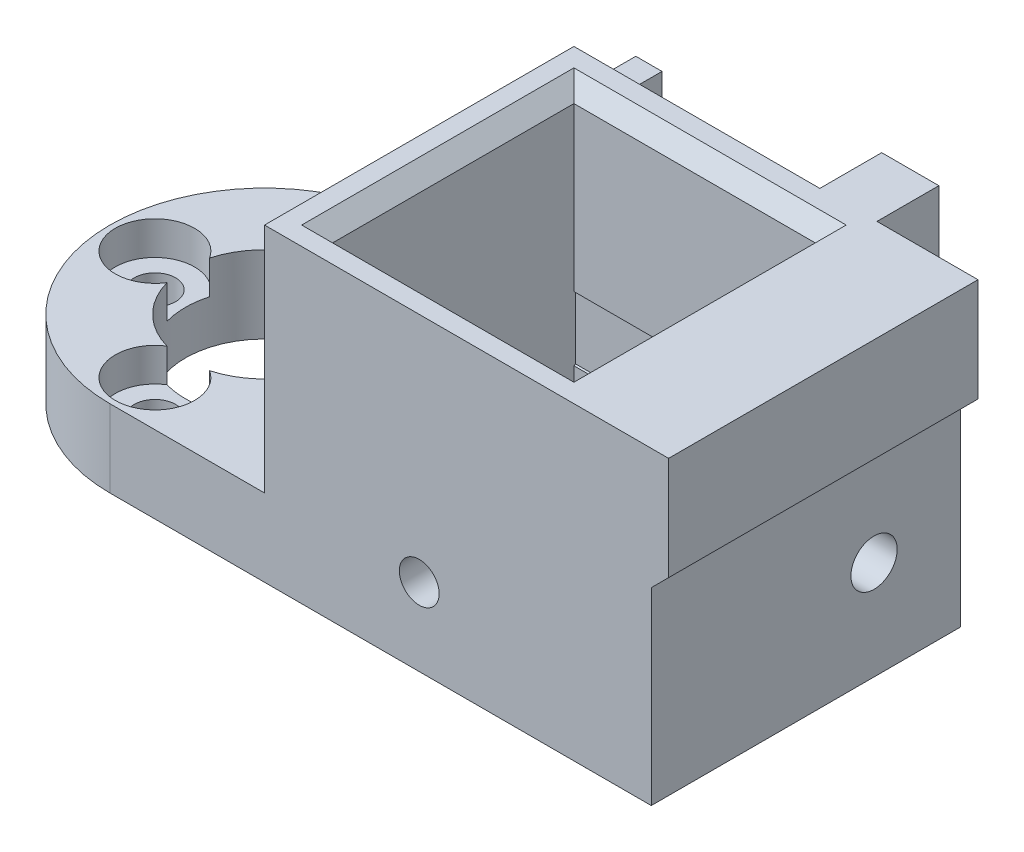
SolidWorks part; units mm, degrees
ref_plane "Front Plane" through (0, 0, 0) normal (0, 0, 1) x (1, 0, 0)
ref_plane "Top Plane" through (0, 0, 0) normal (0, 1, 0) x (1, 0, 0)
ref_plane "Right Plane" through (0, 0, 0) normal (1, 0, 0) x (0, 0, -1)
sketch "Sketch1" plane through (0, 0, 0) normal (0, 1, 0) x (1, 0, 0)
  line L1 (-12.7, 12.7) -> (12.7, 12.7)
  line L2 (-12.7, 12.7) -> (-12.7, -12.7)
  line L3 (-12.7, -12.7) -> (12.7, -12.7)
  line L4 (12.7, 12.7) -> (12.7, -12.7)
  line L5 (-12.7, 12.7) -> (12.7, -12.7) construction
  line L6 (-12.7, -12.7) -> (12.7, 12.7) construction
  line L7 (-9.906, -9.906) -> (9.906, -9.906)
  line L8 (-9.906, -9.906) -> (-9.906, 9.906)
  line L9 (-9.906, 9.906) -> (9.906, 9.906)
  line L10 (9.906, -9.906) -> (9.906, 9.906)
  line L11 (-9.906, -9.906) -> (9.906, 9.906) construction
  line L12 (-9.906, 9.906) -> (9.906, -9.906) construction
  point P0 (0, 0)
  point P6 (0, 0)
  dimension "D1" = 25.4
  dimension "D2" = 19.812
extrude "Boss-Extrude1" add sketch "Sketch1" along normal blind 25.4
sketch "Sketch4" plane through (12.7, 0, 0) normal (1, 0, 0) x (0, 0, -1)
  line L4 (-12.7, 0) -> (12.7, 0)
  line L5 (12.7, 0) -> (12.7, 25.4)
  line L6 (12.7, 25.4) -> (-12.7, 25.4)
  line L7 (-12.7, 25.4) -> (-12.7, 0)
  line L8 (-12.7, 0) -> (12.7, 0)
  line L9 (12.7, 0) -> (12.7, 25.4)
  line L10 (12.7, 25.4) -> (-12.7, 25.4)
  line L11 (-12.7, 25.4) -> (-12.7, 0)
  dimension "D1" = 0
extrude "Boss-Extrude2" add sketch "Sketch4" along normal blind 6.35
hole_wizard "#6 Clearance Hole2" positions "Sketch5" profile "Sketch6" hole size "#6" standard "ANSI Inch"
sketch "Sketch5" plane through (19.05, 0, 0) normal (1, 0, 0) x (0, 0, -1)
  point P0 (5.588, 8.128)
sketch "Sketch6" plane through (19.05, 8.128, -5.588) normal (0, 1, 0) x (0, 0, -1)
  line L0 (0, 0) -> (0, 9.144)
  line L1 (0, 9.144) -> (1.8986, 9.144)
  line L2 (1.8986, 9.144) -> (1.8986, 0)
  line L5 (1.8986, 0) -> (0, 0)
  line L11 (0, -6.35) -> (0, 107.95) construction
  dimension "Thru Hole Dia." = 3.7973
  dimension "Thru Hole Depth" = 9.144
sketch "Sketch7" plane through (9.906, 0, 0) normal (-1, 0, 0) x (0, 0, 1)
  line L1 (-5.588, 13.2606) -> (-10.033, 10.6943)
  line L2 (-10.033, 10.6943) -> (-10.033, 5.5617)
  line L3 (-10.033, 5.5617) -> (-5.588, 2.9954)
  line L4 (-5.588, 2.9954) -> (-1.143, 5.5617)
  line L5 (-1.143, 5.5617) -> (-1.143, 10.6943)
  line L6 (-1.143, 10.6943) -> (-5.588, 13.2606)
  circle A0 centre (-5.588, 8.128) radius 4.445 construction
  dimension "D1" = 8.89
extrude "Cut-Extrude1" cut sketch "Sketch7" against normal blind 5.08 and the other way up to surface other way up to face at (-9.906, 12.7, 0)
sketch "Sketch8" plane through (19.05, 0, 0) normal (1, 0, 0) x (0, 0, -1)
  line L0 (12.7, 15.24) -> (-38.1, 15.24) construction
  line L1 (12.7, 15.24) -> (-38.1, 15.24) construction
  line L2 (12.7, 15.494) -> (-12.7, 15.494)
  line L3 (12.7, 15.494) -> (-38.1, 15.494) construction
  line L7 (-12.7, 25.4) -> (-12.7, 0)
  line L8 (-12.7, 0) -> (12.7, 0)
  line L9 (12.7, 0) -> (12.7, 25.4)
  line L10 (12.7, 25.4) -> (-12.7, 25.4)
  line L11 (-12.7, 25.4) -> (-12.7, 15.494)
  line L13 (12.7, 15.494) -> (12.7, 25.4)
  line L14 (12.7, 25.4) -> (-12.7, 25.4)
  dimension "D1" = 0.254
extrude "Boss-Extrude4" add sketch "Sketch8" along normal up to surface (1.4224 mm away)
sketch "Sketch9" plane through (0, 0, 0) normal (0, -1, 0) x (1, 0, 0)
  line L0 (-12.7, -12.7) -> (-12.7, 12.7) construction
  line L1 (-12.7, -12.7) -> (-12.7, 12.7)
  line L2 (-12.7, 12.7) -> (-38.1, 12.7)
  line L3 (-38.1, 12.7) -> (-38.1, -12.7)
  line L4 (-38.1, -12.7) -> (-12.7, -12.7)
  dimension "D1" = 25.4
extrude "Boss-Extrude5" add sketch "Sketch9" against normal blind 6.35
sketch "Sketch10" plane through (0, 6.35, 0) normal (0, 1, 0) x (1, 0, 0)
  line L0 (-38.1, 12.7) -> (-12.7, 12.7) construction
  line L1 (-38.1, -12.7) -> (-38.1, 12.7) construction
  circle A0 centre (-25.4, 0) radius 6.5
  point P4 (-25.4, 12.7)
  point P7 (-38.1, 0)
  dimension "D1" = 13
extrude "Cut-Extrude2" cut sketch "Sketch10" against normal up to next
hole_wizard "M3 Clearance Hole1" positions "Sketch12" profile "Sketch13" hole size "M3" standard "ANSI Metric" end condition up to next
sketch "Sketch12" plane through (0, 6.35, 0) normal (0, 1, 0) x (1, 0, 0)
  line L0 (-38.1, 12.7) -> (-12.7, 12.7) construction
  circle A0 centre (-25.4, 0) radius 6.5 construction
  point P0 (-25.4, 9)
  point P9 (-25.4, 12.7)
  dimension "D1" = 9
sketch "Sketch13" plane through (-25.4, 6.35, -9) normal (1, 0, 0) x (0, 0, 1)
  line L0 (0, 0) -> (0, 6.35)
  line L1 (0, 6.35) -> (1.7, 6.35)
  line L2 (1.7, 6.35) -> (1.7, 0)
  line L5 (1.7, 0) -> (0, 0)
  line L11 (0, -6.35) -> (0, 107.95) construction
  dimension "Thru Hole Dia." = 3.4
  dimension "Thru Hole Depth" = 6.35
pattern_circular "CirPattern1" count 4 over 360 about axis through (-25.4, 0, 0) along (0, 1, 0) of "M3 Clearance Hole1"
fillet "Fillet1" radius 12.7 2 edges at (-38.1, 3.175, 12.7) (-38.1, 3.175, -12.7)
sketch "Sketch15" plane through (0, 0, 0) normal (0, -1, 0) x (1, 0, 0)
  line L0 (9.906, -9.906) -> (-9.906, -9.906) construction
  line L1 (9.906, 9.906) -> (9.906, -9.906) construction
  line L2 (-9.906, 9.906) -> (9.906, 9.906) construction
  line L3 (-9.906, -9.906) -> (-9.906, 9.906) construction
  line L4 (9.906, -9.906) -> (-9.906, -9.906)
  line L5 (9.906, 9.906) -> (9.906, -9.906)
  line L6 (-9.906, 9.906) -> (9.906, 9.906)
  line L7 (-9.906, -9.906) -> (-9.906, 9.906)
  line L8 (-8.001, 8.001) -> (8.001, 8.001)
  line L9 (8.001, 8.001) -> (8.001, -8.001)
  line L10 (8.001, -8.001) -> (-8.001, -8.001)
  line L11 (-8.001, -8.001) -> (-8.001, 8.001)
  dimension "D1" = 1.905
extrude "Boss-Extrude6" add sketch "Sketch15" against normal blind 2.54
sketch "Sketch17" plane through (0, 6.35, 0) normal (0, 1, 0) x (1, 0, 0)
  circle A0 centre (-25.4, 9) radius 3.25
  dimension "D1" = 6.5
extrude "Cut-Extrude4" cut sketch "Sketch17" against normal offset from surface (2.75 mm away) 2.75 up to face at (-34.4, 6.35, 1.7)
pattern_circular "CirPattern2" count 4 over 360 about axis through (-25.4, 0, 0) along (0, 1, 0) of "Cut-Extrude4"
fillet "Fillet4" radius 1.27 8 edges at (0, 2.54, 8.001) (0, 0, 8.001) (-8.001, 2.54, 0) (8.001, 2.54, 0) (-8.001, 0, 0) (8.001, 0, 0) (0, 2.54, -8.001) (0, 0, -8.001)
hole_wizard "#4 Clearance Hole1" positions "Sketch20" profile "Sketch21" hole size "#4" standard "ANSI Inch" end condition through all
sketch "Sketch20" plane through (0, 0, -12.7) normal (0, 0, -1) x (-1, 0, 0)
  line L0 (-9.906, 25.4) -> (9.906, 25.4) construction
  line L1 (-19.05, 0) -> (25.4, 0) construction
  point P0 (0, 6.35)
  point P5 (0, 25.4)
  dimension "D1" = 6.35
sketch "Sketch21" plane through (0, 6.35, -12.7) normal (1, 0, 0) x (0, 1, 0)
  line L0 (0, 0) -> (0, 25.4)
  line L1 (0, 25.4) -> (1.6319, 25.4)
  line L2 (1.6319, 25.4) -> (1.6319, 0)
  line L5 (1.6319, 0) -> (0, 0)
  line L11 (0, -6.35) -> (0, 107.95) construction
  dimension "Thru Hole Dia." = 3.2639
  dimension "Thru Hole Depth" = 25.4
chamfer "Chamfer1" distance 1.4224 angle 45 1 edges at (20.4724, 15.494, 0)
chamfer "Chamfer2" distance 1.27 angle 45 4 edges at (0, 25.4, 9.906) (9.906, 25.4, 0) (0, 25.4, -9.906) (-9.906, 25.4, 0)
sketch "Sketch22" plane through (0, 0, -12.7) normal (0, 0, -1) x (-1, 0, 0)
  line L0 (-19.05, 0) -> (25.4, 0) construction
  line L1 (7.62, 0) -> (-2.54, 0)
  line L2 (7.62, 0) -> (7.62, 2.54)
  line L3 (7.62, 2.54) -> (-2.54, 2.54)
  line L4 (-2.54, 0) -> (-2.54, 2.54)
  line L5 (12.7, 25.4) -> (12.7, 6.35) construction
  dimension "D1" = 2.54
  dimension "D2" = 10.16
  dimension "D3" = 5.08
extrude "Boss-Extrude7" add sketch "Sketch22" along normal blind 5.08
chamfer "Chamfer3" distance 2.54 angle 45 2 edges at (-7.62, 1.27, -17.78) (2.54, 1.27, -17.78)
sketch "Sketch23" plane through (0, 0, -12.7) normal (0, 0, -1) x (-1, 0, 0)
  line L0 (-20.4724, 25.4) -> (12.7, 25.4) construction
  line L1 (12.7, 25.4) -> (12.7, 6.35) construction
  line L2 (-20.4724, 25.4) -> (12.7, 25.4)
  line L3 (12.7, 25.4) -> (12.7, 6.35)
  line L4 (12.7, 22.16) -> (10.547, 22.16)
  line L5 (10.547, 22.16) -> (10.547, 12.152)
  line L6 (10.547, 12.152) -> (9.023, 12.152)
  line L7 (9.023, 12.152) -> (9.023, 9.999)
  line L8 (9.023, 9.999) -> (12.7, 9.999)
  line L9 (-10.027, 12.66) -> (-12.18, 12.66)
  line L10 (-12.18, 12.66) -> (-12.18, 25.4)
  line L11 (-12.18, 25.4) -> (-7.487, 25.4)
  line L12 (-7.487, 25.4) -> (-7.487, 23.368)
  line L13 (-7.487, 23.368) -> (-10.027, 23.368)
  line L14 (-10.027, 23.368) -> (-10.027, 12.66)
  line L15 (-0.7436, 22.86) -> (-8.64, 22.86) construction
  line L16 (-10.027, 12.66) -> (-9.64, 12.66) construction
  line L17 (-9.64, 13.16) -> (-9.64, 21.86) construction
  line L18 (10.547, 22.16) -> (10.16, 22.16) construction
  line L19 (10.16, 13.16) -> (10.16, 21.16) construction
  line L20 (9.16, 22.16) -> (0.1636, 22.16) construction
  line L21 (-6.79, 12.66) -> (-9.14, 12.66) construction
  line L24 (9.66, 12.66) -> (7.21, 12.66) construction
  point P27 (-7.487, 23.368)
  point P30 (-10.027, 23.368)
  point P31 (10.547, 22.16)
  dimension "D1" = 0.508
  dimension "D2" = 20.574
  dimension "D3" = 2.54
  dimension "D4" = 0.508
  dimension "D5" = 1.524
extrude "Boss-Extrude8" add sketch "Sketch23" along normal blind 5.08 contours L7 L8 L3 L4 L5 L6 | L14 L13 L12 L2 L10 L9
sketch "Sketch24" plane through (12.18, 0, 0) normal (1, 0, 0) x (0, 0, -1)
  line L0 (17.78, 12.66) -> (12.7, 12.66) construction
  line L1 (17.78, 12.66) -> (12.7, 12.66)
  line L2 (17.78, 12.66) -> (12.7, 7.58)
  line L3 (12.7, 7.58) -> (12.7, 12.66)
extrude "Boss-Extrude9" add sketch "Sketch24" against normal up to surface (2.153 mm away) up to face at (10.027, 18.014, -15.24)
sketch "Sketch25" plane through (-12.7, 0, 0) normal (-1, 0, 0) x (0, 0, 1)
  line L0 (-17.78, 9.999) -> (-12.7, 9.999) construction
  line L1 (-17.78, 9.999) -> (-12.7, 9.999)
  line L2 (-17.78, 9.999) -> (-12.7, 4.919)
  line L3 (-12.7, 4.919) -> (-12.7, 9.999)
extrude "Boss-Extrude10" add sketch "Sketch25" against normal up to surface (3.677 mm away) up to face at (-9.023, 11.0755, -15.24)
equation "\"TOL\"= .01"
equation "\"D1@Sketch8\"=\"TOL\""
equation "\"D2@Sketch1\"=.76+\"TOL\"*2"
